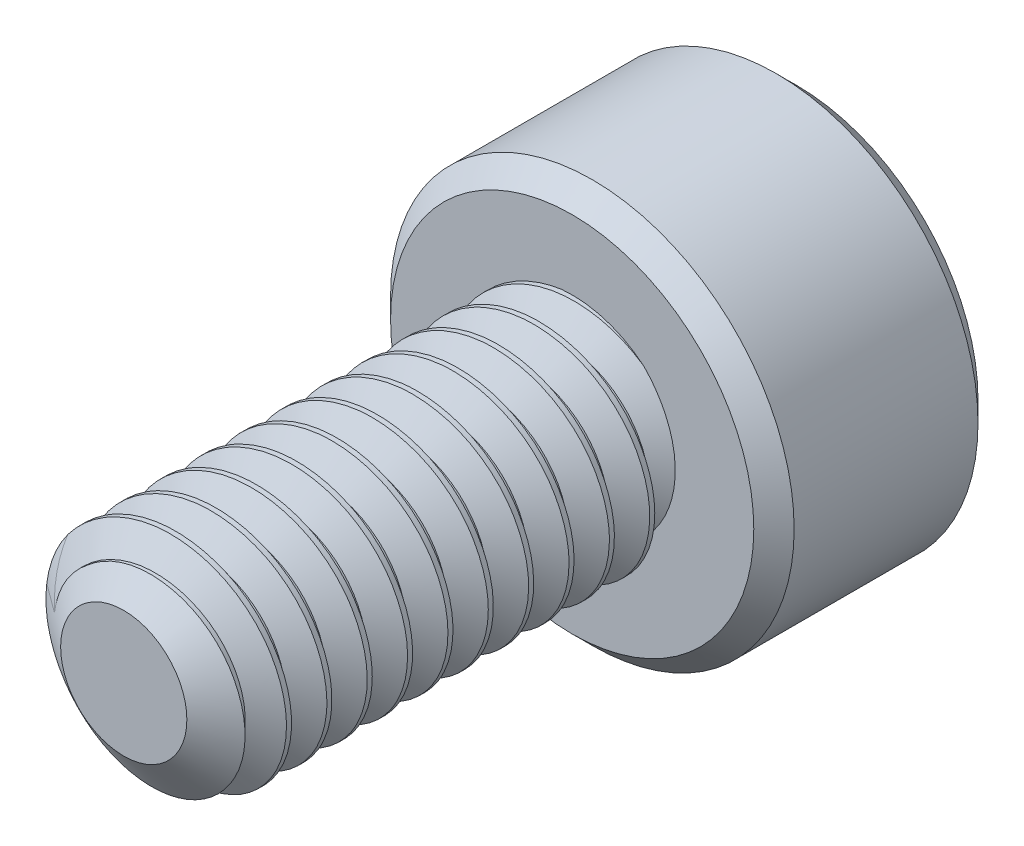
SolidWorks part; units mm, degrees
ref_plane "Front Plane" through (0, 0, 0) normal (0, 0, 1) x (1, 0, 0)
ref_plane "Top Plane" through (0, 0, 0) normal (0, 1, 0) x (1, 0, 0)
ref_plane "Right Plane" through (0, 0, 0) normal (1, 0, 0) x (0, 0, -1)
sketch "Sketch1" plane through (0, 0, 0) normal (0, 0, 1) x (1, 0, 0)
  circle A0 centre (0, 0) radius 1.25
  dimension "OD" = 2.5
extrude "Extrude1" add sketch "Sketch1" against normal blind 5
sketch "Sketch2" plane through (0, 0, 0) normal (0, 0, 1) x (1, 0, 0)
  circle A0 centre (0, 0) radius 1.25 construction
  circle A1 centre (0, 0) radius 1.25
curve "Helix/Spiral1" pitch 0.45 height 5.45 radius 1.25 centre (0, 0, 0) axis (0, 0, -1) start towards (0, 1, 0) parameters "pitch"=0.45
sketch "Sketch3" plane through (0, 0, 0) normal (1, 0, 0) x (0, 0, -1)
  line L0 (-0.3938, 1.25) -> (-0.225, 0.9577)
  line L1 (-0.225, 0.9577) -> (-0.1688, 0.9577)
  line L2 (-0.1688, 0.9577) -> (0, 1.25)
  line L3 (-0.3938, 1.25) -> (0, 1.25)
  line L4 (-0.1969, 1.25) -> (-0.1969, 0.9577) construction
  line L5 (-0.3094, 1.1039) -> (-0.0844, 1.1039) construction
  line L6 (0, 1.25) -> (0, -1.25) construction
  dimension "D1" = 0.0563
  dimension "D2" = 0.225
  dimension "D3" = 60
sweep "Cut-Sweep1" cut profiles "Sketch3" path "Helix/Spiral1"
sketch "Sketch4" plane through (0, 0, 0) normal (1, 0, 0) x (0, 0, -1)
  line L0 (0.3825, 1.25) -> (0, 0.7037)
  line L1 (0, 0.7037) -> (0, 1.25)
  line L2 (0.3825, 1.25) -> (0, 1.25)
  line L3 (-0.3938, 1.25) -> (0, 1.25) construction
  line L4 (0, 0) -> (7.0209, 0) construction
  dimension "D1" = 55
  dimension "D2" = 0.254
revolve "Cut-Revolve1" cut sketch "Sketch4" angle 360 about L4
sketch "Sketch5" plane through (0, 0, 0) normal (1, 0, 0) x (0, 0, -1)
  line L0 (5, -0.738) -> (5, 1.2445) construction
  line L1 (5, 1.377) -> (87.4327, 1.377)
  line L2 (5, 1.377) -> (5, 0)
  line L3 (5, 0) -> (87.3125, 0)
  line L4 (87.3125, 1.0468) -> (87.3125, 0)
  line L5 (87.4327, 1.377) -> (87.3125, 1.0468)
  line L6 (0, 0) -> (9.9695, 0) construction
  point P3 (87.3125, 1.377)
  point P10 (87.3125, 1.377)
  dimension "D1" = 0.3302
  dimension "Thread min" = 87.3125
  dimension "D2" = 0.127
  dimension "D3" = 20
revolve "partially thread" [suppressed] add sketch "Sketch5" angle 360 about L6
sketch "Sketch6" plane through (0, 0, -5) normal (0, 0, -1) x (-1, 0, 0)
  circle A0 centre (0, 0) radius 2.25
  dimension "head dia" = 4.5
extrude "Extrude2" add sketch "Sketch6" along normal blind 2.5
sketch "Sketch7" plane through (0, 0, -7.5) normal (0, 0, -1) x (-1, 0, 0)
  line L1 (0, 1.1547) -> (-1, 0.5774)
  line L2 (-1, 0.5774) -> (-1, -0.5774)
  line L3 (-1, -0.5774) -> (0, -1.1547)
  line L4 (0, -1.1547) -> (1, -0.5774)
  line L5 (1, -0.5774) -> (1, 0.5774)
  line L6 (1, 0.5774) -> (0, 1.1547)
  circle A0 centre (0, 0) radius 1 construction
  dimension "hex dia" = 2
extrude "Cut-Extrude1" cut sketch "Sketch7" against normal blind 1.5
sketch "Sketch8" plane through (0, 0, -7.5) normal (0, 0, -1) x (-1, 0, 0)
  circle A0 centre (0, 0) radius 1.1547
extrude "Cut-Extrude2" cut sketch "Sketch8" against normal through all draft 45
chamfer "Chamfer1" distance 0.225 angle 45 2 edges at (-2.25, 0, -7.5) (-2.25, 0, -5)
sketch "Sketch9" plane through (0, 0, 0) normal (1, 0, 0) x (0, 0, -1)
  line L0 (0, 1.25) -> (0, -1.25) construction
  line L1 (2.475, 1.25) -> (2.475, -1.25) construction
  dimension "D1" = 2.475
equation "\"D3@Helix/Spiral1\" = \"screw length@Extrude1\"+\"pitch@Helix/Spiral1\""
equation "\"D1@Sketch3\" = \"pitch@Helix/Spiral1\"*.125"
equation "\"D2@Sketch3\" = \"pitch@Helix/Spiral1\"*.5"
equation "\"D1@Cut-Extrude1\" = \"hex dia@Sketch7\"*.75"
equation "\"D1@Chamfer1\" = \"head dia@Sketch6\"*.05"
equation "\"D1@Sketch9\" = \"pitch@Helix/Spiral1\"*5.5"
